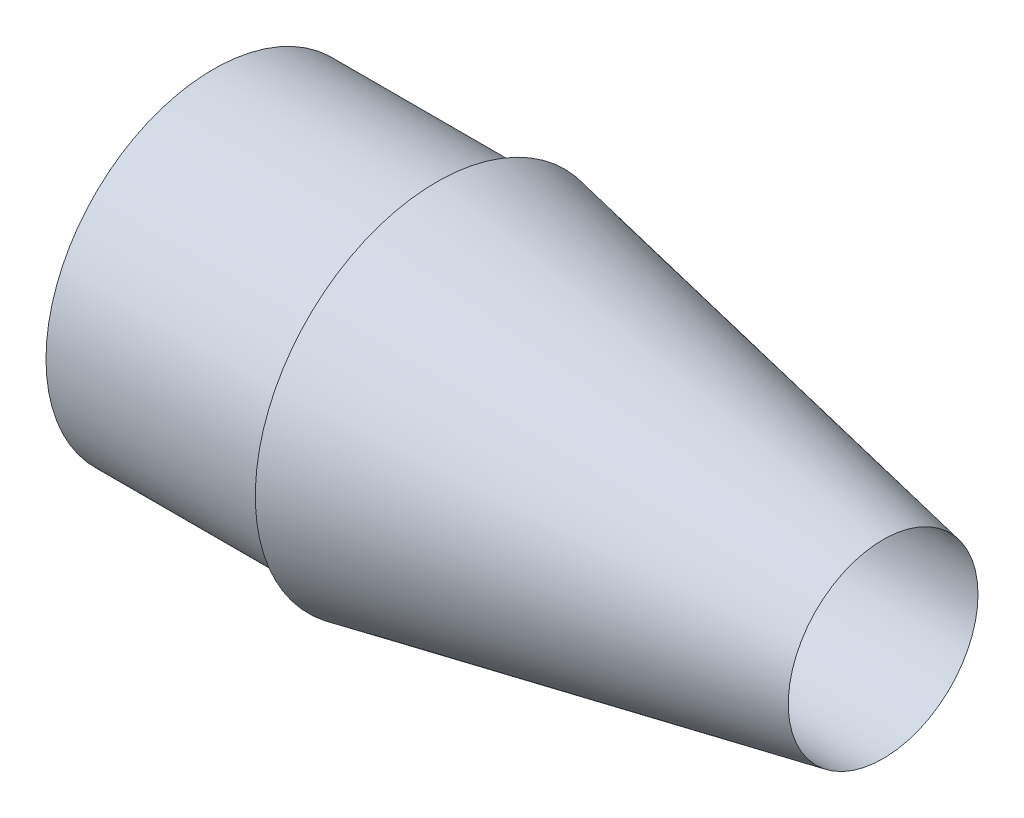
SolidWorks part; units mm, degrees
ref_plane "Front Plane" through (0, 0, 0) normal (0, 0, 1) x (1, 0, 0)
ref_plane "Top Plane" through (0, 0, 0) normal (0, 1, 0) x (1, 0, 0)
ref_plane "Right Plane" through (0, 0, 0) normal (1, 0, 0) x (0, 0, -1)
sketch "Sketch2" plane through (0, 0, 0) normal (0, 0, 1) x (1, 0, 0)
  line L0 (0, 21.59) -> (101.6, 21.59)
  line L1 (101.6, 21.59) -> (0, 41.275)
  line L2 (0, 41.275) -> (0, 38.1)
  line L3 (0, 38.1) -> (-50.8, 38.1)
  line L5 (-50.8, 38.1) -> (0, 19.05)
  line L6 (0, 19.05) -> (0, 21.59)
  dimension "D1" = 101.6
  dimension "D2" = 21.59
  dimension "D3" = 41.275
  dimension "D4" = 38.1
  dimension "D5" = 50.8
  dimension "D6" = 19.05
ref_axis "Axis1" through (109.22, 0, 0) along (-1, 0, 0)
revolve "Revolve1" add sketch "Sketch2" angle 360 about axis through (109.22, 0, 0) along (-1, 0, 0)
